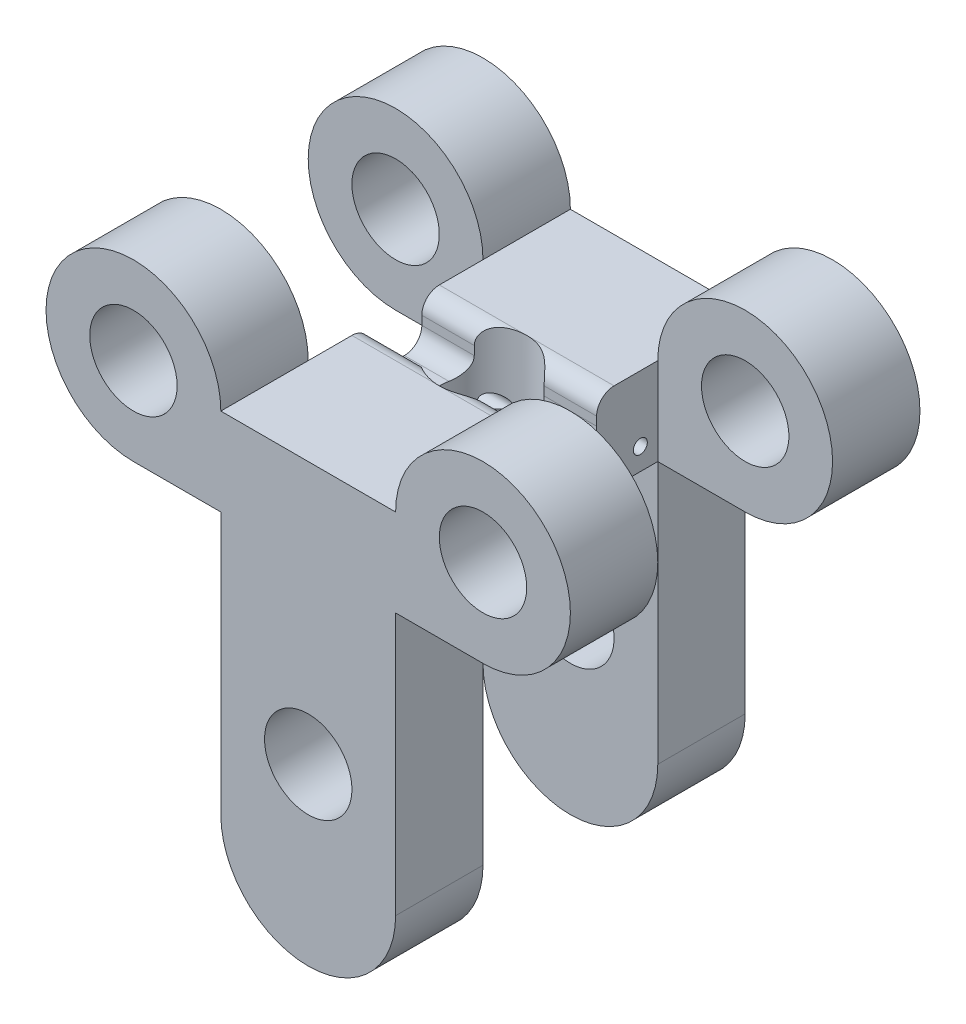
SolidWorks part; units mm, degrees
ref_plane "前视基准面" through (0, 0, 0) normal (0, 0, 1) x (1, 0, 0)
ref_plane "上视基准面" through (0, 0, 0) normal (0, 1, 0) x (1, 0, 0)
ref_plane "右视基准面" through (0, 0, 0) normal (1, 0, 0) x (0, 0, -1)
other "Configuration Table"
sketch "Sketch1" plane through (0, 0, 0) normal (0, 0, 1) x (1, 0, 0)
  line L0 (0, 0) -> (10, 0) construction
  line L1 (5, 0) -> (5, 3.3087) construction
  line L2 (0, -2.5) -> (10, -2.5)
  line L3 (10, -2.5) -> (10, 0)
  line L4 (10, 0) -> (0, 0)
  circle A0 centre (0, 0) radius 1.25
  circle A1 centre (0, 0) radius 2.5
  circle A4 centre (10, 0) radius 1.25
  circle A5 centre (10, 0) radius 2.5
  dimension "D1" = 2.5
  dimension "D2" = 5
  dimension "D3" = 10
extrude "Boss-Extrude1" add sketch "Sketch1" along normal mid plane 10 contours A1 A0 | A1 L2 L3 L4 | A5 L4 A4 L3 | A5 L3 A4 L4 region at (5, -1.3722, 0) region at (-1.7178, 1.7178, 0) region at (8.7621, -1.2379, 0) region at (10.0707, -1.875, 0)
sketch "Sketch2" plane through (0, 0, 0) normal (0, 1, 0) x (1, 0, 0)
  line L0 (5, 5) -> (5, -5) construction
  line L1 (7.5, 5) -> (2.5, 5) construction
  line L2 (7.5, -5) -> (2.5, -5) construction
  line L3 (5, -5) -> (5, 0) construction
  line L4 (5, 0) -> (10, 0) construction
  circle A0 centre (5, 0) radius 1.25
  circle A1 centre (10, 0) radius 1.25
  circle A2 centre (0, 0) radius 1.25
  dimension "D1" = 2.5
  dimension "D3" = 2.5
  dimension "D2" = 5
extrude "Cut-Extrude1" cut sketch "Sketch2" against normal blind 5 contours A0 region at (5, 0, 0)
sketch "Sketch4" plane through (0, 0, 0) normal (0, 1, 0) x (1, 0, 0)
  line L0 (2.5, -5) -> (2.5, 5) construction
  line L1 (-2.5, -2.5) -> (2.5, -2.5)
  line L2 (-2.5, -2.5) -> (-2.5, 2.5)
  line L3 (-2.5, 2.5) -> (2.5, 2.5)
  line L4 (2.5, -2.5) -> (2.5, 2.5)
  line L5 (-2.5, -2.5) -> (2.5, 2.5) construction
  line L6 (-2.5, 2.5) -> (2.5, -2.5) construction
  line L7 (5, 5) -> (5, -5) construction
  line L8 (7.5, 5) -> (2.5, 5) construction
  line L9 (7.5, -5) -> (2.5, -5) construction
  line L10 (7.5, -2.5) -> (7.5, 2.5)
  line L11 (12.5, -2.5) -> (7.5, -2.5)
  line L12 (12.5, 2.5) -> (7.5, 2.5)
  line L13 (12.5, -2.5) -> (12.5, 2.5)
  point P0 (0, 0)
  dimension "D1" = 5
extrude "Cut-Extrude2" cut sketch "Sketch4" against normal through all both and the other way through all
sketch "Sketch5" plane through (0, 0, 0) normal (0, 1, 0) x (1, 0, 0)
  line L5 (7.5, -2.5) -> (7.5, 2.5) construction
  line L6 (2.5, -0.75) -> (7.5, -0.75)
  line L7 (2.5, -0.75) -> (2.5, 0.75)
  line L8 (2.5, 0.75) -> (7.5, 0.75)
  line L9 (7.5, -0.75) -> (7.5, 0.75)
  line L10 (2.5, -0.75) -> (7.5, 0.75) construction
  line L11 (2.5, 0.75) -> (7.5, -0.75) construction
  point P0 (5, 0)
  dimension "D1" = 1.5
extrude "Cut-Extrude3" cut sketch "Sketch5" against normal blind 1.25
sketch "Sketch6" plane through (7.5, 0, 0) normal (1, 0, 0) x (0, 0, -1)
  line L0 (0, -1.25) -> (0, -2.5) construction
  line L1 (-0.75, -1.25) -> (0.75, -1.25) construction
  line L2 (2.5, -2.5) -> (-2.5, -2.5) construction
  line L3 (0, -2.5) -> (0, -1.875) construction
  line L4 (0, -1.875) -> (0.7288, -1.875) construction
  circle A0 centre (0, -1.875) radius 0.2
  circle A1 centre (1, -1.875) radius 0.2
  circle A2 centre (2, -1.875) radius 0.2
  circle A3 centre (-1, -1.875) radius 0.2
  circle A4 centre (-2, -1.875) radius 0.2
  dimension "D1" = 0.4
  dimension "D4" = 1
  dimension "D5" = 1
  dimension "D2" = 3
  dimension "D3" = 3
extrude "Cut-Extrude4" cut sketch "Sketch6" against normal through all
fillet "Fillet1" radius 0.5 8 edges at (6.75, -1.25, 0.75) (3.25, -1.25, 0.75) (3.25, -1.25, -0.75) (6.75, -1.25, -0.75) (6.75, 0, 0.75) (6.75, 0, -0.75) (3.25, 0, 0.75) (3.25, 0, -0.75)
sketch "Sketch7" plane through (0, 0, 5) normal (0, 0, 1) x (1, 0, 0)
  line L0 (2.5, -2.5) -> (2.5, -12.5)
  line L1 (2.5, -12.5) -> (7.5, -12.5)
  line L2 (7.5, -12.5) -> (7.5, -2.5)
  line L4 (7.5, -2.5) -> (2.5, -2.5)
  dimension "D1" = 10
extrude "Boss-Extrude2" add sketch "Sketch7" against normal blind 10
sketch "Sketch9" plane through (0, 0, -5) normal (0, 0, -1) x (-1, 0, 0)
  line L0 (-7.5, -2.5) -> (-2.5, -2.5) construction
  line L1 (-5, -7.5) -> (-5, -12.5) construction
  line L2 (-2.5, -12.5) -> (-7.5, -12.5) construction
  circle A0 centre (-5, -7.5) radius 1.25
  dimension "D1" = 2.5
  dimension "D2" = 5
extrude "Cut-Extrude6" cut sketch "Sketch9" against normal blind 10
sketch "Sketch11" plane through (7.5, 0, 0) normal (1, 0, 0) x (0, 0, -1)
  line L0 (-5, -12.5) -> (5, -12.5) construction
  line L1 (5, -12.5) -> (0, -12.5) construction
  line L3 (-2.5, -22.5) -> (2.5, -22.5)
  line L4 (-2.5, -22.5) -> (-2.5, -2.5)
  line L5 (-2.5, -2.5) -> (2.5, -2.5)
  line L6 (2.5, -22.5) -> (2.5, -2.5)
  line L7 (-2.5, -22.5) -> (2.5, -2.5) construction
  line L8 (-2.5, -2.5) -> (2.5, -22.5) construction
  dimension "D1" = 5
  dimension "D2" = 20
extrude "Cut-Extrude7" cut sketch "Sketch11" against normal blind 10
fillet "Fillet3" radius 2.5 4 edges at (2.5, -12.5, 3.75) (7.5, -12.5, 3.75) (2.5, -12.5, -3.75) (7.5, -12.5, -3.75)
